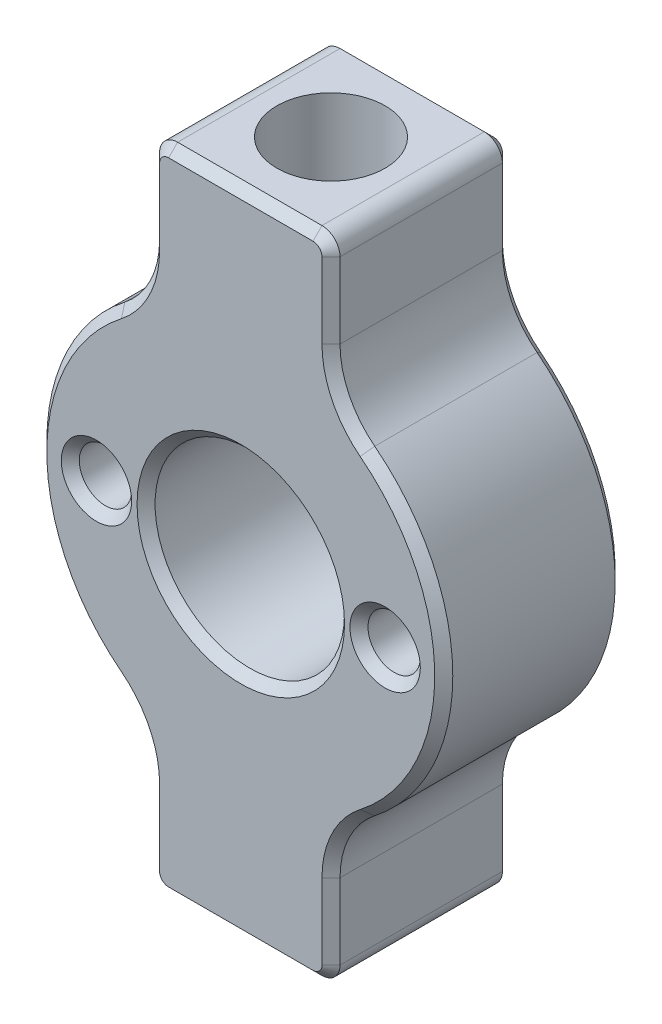
SolidWorks part; units mm, degrees
ref_plane "Front" through (0, 0, 0) normal (0, 0, 1) x (1, 0, 0)
ref_plane "Top" through (0, 0, 0) normal (0, 1, 0) x (1, 0, 0)
ref_plane "Right" through (0, 0, 0) normal (1, 0, 0) x (0, 0, -1)
sketch "Skizze1" plane through (0, 0, 0) normal (0, 0, 1) x (1, 0, 0)
  circle A0 centre (0, 0) radius 5.25
  circle A1 centre (0, 0) radius 11.25
  dimension "D1" = 10.5
  dimension "D2" = 6
extrude "Aufsatz-Linear austragen1" add sketch "Skizze1" along normal blind 10
sketch "Skizze2" plane through (0, 0, 0) normal (0, 1, 0) x (1, 0, 0)
  line L0 (0, 0) -> (0, -10) construction
  line L3 (-11.25, -10) -> (11.25, -10) construction
  line L4 (5.25, 0) -> (-5.25, 0) construction
  line L5 (-5, -10) -> (5, -10)
  line L6 (-5, -10) -> (-5, 0)
  line L7 (-5, 0) -> (5, 0)
  line L8 (5, -10) -> (5, 0)
  line L9 (-5, -10) -> (5, 0) construction
  line L10 (-5, 0) -> (5, -10) construction
  point P4 (0, -5)
extrude "Aufsatz-Linear austragen2" add sketch "Skizze2" along normal blind 12 from offset 6
sketch "Skizze3" plane through (0, 18, 0) normal (0, 1, 0) x (1, 0, 0)
  line L0 (0, 0) -> (0, -10) construction
  line L1 (-5, -10) -> (5, -10) construction
  circle A0 centre (0, -5) radius 3
  dimension "D1" = 6
extrude "Schnitt-Linear austragen1" cut sketch "Skizze3" against normal blind 10
mirror "Spiegeln1" about plane through (0, 0, 0) normal (0, 1, 0) of "Schnitt-Linear austragen1", "Aufsatz-Linear austragen2"
sketch "Skizze4" plane through (0, 0, 10) normal (0, 0, 1) x (1, 0, 0)
  line L0 (0, 0) -> (0, 11.1324) construction
  line L1 (0, 0) -> (13.0739, 0) construction
  circle A2 centre (8, 0) radius 1.45
  circle A3 centre (-8, 0) radius 1.45
  dimension "D1" = 16
  dimension "D2" = 2.9
extrude "Schnitt-Linear austragen2" cut sketch "Skizze4" against normal blind 8
fillet "Verrundung2" radius 5 4 edges at (-5, -10.0778, 5) (-5, 10.0778, 5) (5, 10.0778, 5) (5, -10.0778, 5)
fillet "Verrundung1" radius 1 4 edges at (-5, 18, 5) (5, 18, 5) (5, -18, 5) (-5, -18, 5)
chamfer "Fase1" distance 0.5 angle 45 36 edges at (5.25, 0, 10) (-5, 14.9043, 10) (0, 18, 10) (5, 14.9043, 10) (5, -14.9043, 10) (0, -18, 10) (-5, -14.9043, 10) (5.25, 0, 0) (5, 14.9043, 0) (0, 18, 0) (-5, 14.9043, 0) (-5, -14.9043, 0) (0, -18, 0) (5, -14.9043, 0) (5.5064, 10.616, 10) (11.25, 0, 10) (5.5064, -10.616, 10) (-5.5064, -10.616, 10) (-11.25, 0, 10) (-5.5064, 10.616, 10) (5.5064, 10.616, 0) (-5.5064, 10.616, 0) (-11.25, 0, 0) (-5.5064, -10.616, 0) (5.5064, -10.616, 0) (11.25, 0, 0) (-9.45, 0, 10) (9.45, 0, 10) (4.7071, 17.7071, 10) (4.7071, -17.7071, 10) (-4.7071, -17.7071, 10) (-4.7071, 17.7071, 10) (-4.7071, -17.7071, 0) (4.7071, -17.7071, 0) (4.7071, 17.7071, 0) (-4.7071, 17.7071, 0)
